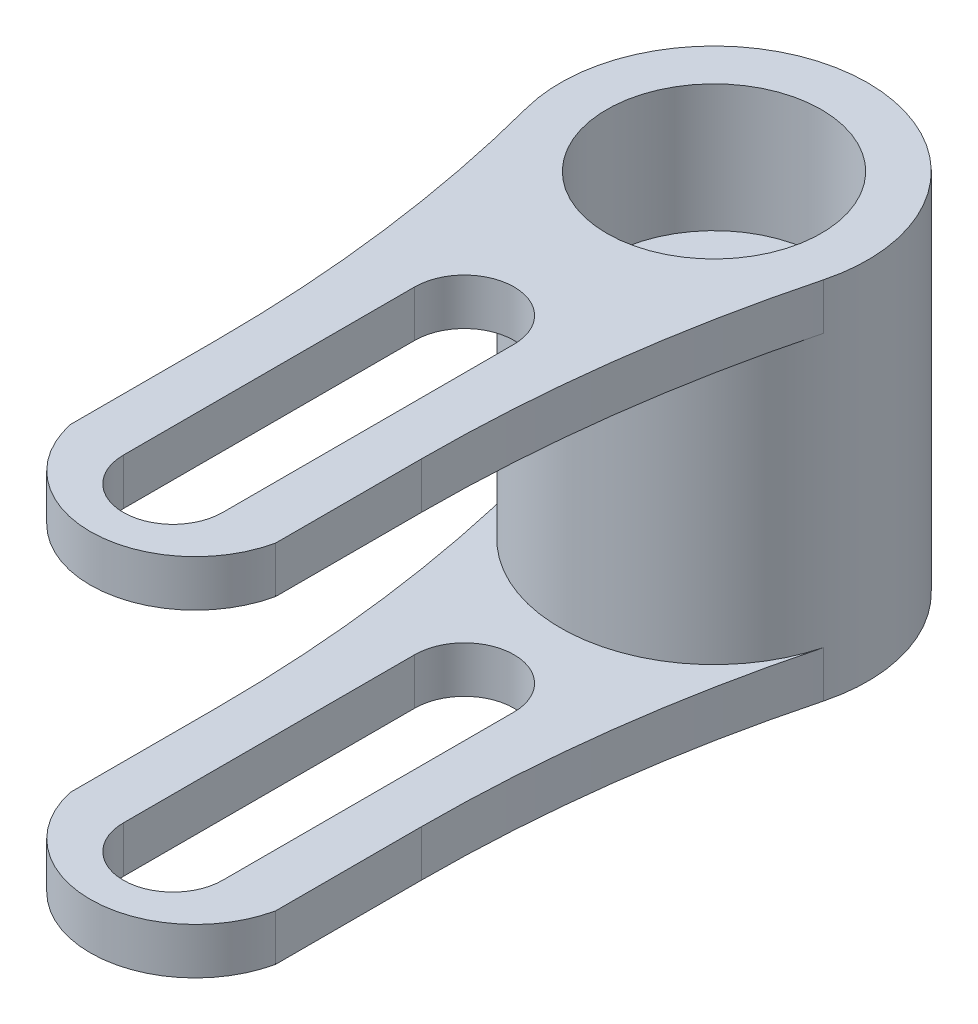
SolidWorks part; units mm, degrees
other "Camera1"
ref_plane "Front Plane" through (0, 0, 0) normal (0, 0, 1) x (1, 0, 0)
ref_plane "Top Plane" through (0, 0, 0) normal (0, 1, 0) x (1, 0, 0)
ref_plane "Right Plane" through (0, 0, 0) normal (1, 0, 0) x (0, 0, -1)
sketch "Sketch1" plane through (0, 0, 0) normal (0, 1, 0) x (1, 0, 0)
  line L0 (0, 5.8) -> (0, 4.05) construction
  line L1 (0, -9.425) -> (0, -20.425) construction
  line L2 (-3.875, -14.925) -> (-3.875, -20.425)
  line L3 (3.875, -20.425) -> (3.875, -14.925)
  line L4 (1.875, -9.425) -> (1.875, -20.425)
  line L5 (-1.875, -9.425) -> (-1.875, -20.425)
  line L6 (0, -7.55) -> (0, -5.8) construction
  line L7 (-3.875, -14.925) -> (3.875, -14.925) construction
  circle A0 centre (0, 0) radius 4.05
  circle A1 centre (0, 0) radius 5.8
  arc A2 (1.875, -9.425) -> (-1.875, -9.425) centre (0, -9.425) ccw
  arc A3 (-5.6102, -1.4717) -> (-3.875, -14.925) centre (-56.8961, -14.925) cw
  arc A4 (-3.875, -20.425) -> (3.875, -20.425) centre (0, -20.425) ccw
  arc A5 (3.875, -14.925) -> (5.6102, -1.4717) centre (56.8961, -14.925) cw
  arc A6 (-1.875, -20.425) -> (1.875, -20.425) centre (0, -20.425) ccw
  point P6 (0, -14.925)
  dimension "D1" = 8.1
  dimension "D2" = 1.75
  dimension "D3" = 3.75
  dimension "D4" = 2
  dimension "D5" = 11
  dimension "D6" = 1.75
extrude "Boss-Extrude1" add sketch "Sketch1" along normal mid plane 13.775 contours L3 A5 A1 A3 L2 A4 A6 L5 A2 L4 | A0 | A1 A0 region at (-4.0583, 0, 8.1101) region at (-0.7209, 0, -5.5897) region at (0, 0, 0)
ref_plane "Plane1" through (0, -5.1375, 0) normal (0, -1, 0) x (-1, 0, 0)
ref_plane "Plane2" through (0, 5.1375, 0) normal (0, 1, 0) x (1, 0, 0)
extrude "Cut-Extrude1" cut sketch "Sketch1<4>" along normal up to surface (10.275 mm away) from surface contours L3 A5 A1 A3 L2 A4 A6 L5 A2 L4 region at (-4.0583, 0, 8.1101) up to plane "Plane2" starting at plane "Plane1"
sketch "Sketch1<4>" plane through (0, 0, 0) normal (0, 1, 0) x (1, 0, 0) same geometry as "Sketch1"
extrude "Cut-Extrude2" cut sketch "Sketch1<5>" against normal blind 4.8 from surface contours A0 region at (0, 0, 0) starting at face at (0, 6.8875, 14.925)
sketch "Sketch1<5>" plane through (0, 0, 0) normal (0, 1, 0) x (1, 0, 0) same geometry as "Sketch1"
sketch "Sketch4" plane through (0, -6.8875, 0) normal (0, -1, 0) x (1, 0, 0)
  line L2 (0, 23.55) -> (0, 24.3) construction
  line L4 (0, 23.55) -> (0, 22.3) construction
  arc A0 (3.875, 20.425) -> (-3.875, 20.425) centre (0, 20.425) ccw construction
  arc A1 (1.875, 20.425) -> (-1.875, 20.425) centre (0, 20.425) ccw construction
  arc A3 (-3.875, 20.425) -> (3.875, 20.425) centre (0, 19.585) cw
  arc A4 (3.875, 20.425) -> (-3.875, 20.425) centre (0, 20.425) ccw
  dimension "D1" = 0.75
extrude "Cut-Extrude3" cut sketch "Sketch4" against normal through all
sketch "Sketch6" plane through (0, 0, 0) normal (0, 1, 0) x (1, 0, 0)
  arc A0 (5.6102, -1.4717) -> (-5.6102, -1.4717) centre (0, 0) ccw construction
  point P0 (-5.8, 0)
ref_plane "Plane3" through (-5.8, 0, 0) normal (1, 0, 0) x (0, 0, -1)
equation "\"D1@Boss-Extrude1\"=9.525mm+1.75mm+1.75mm+.75mm"
